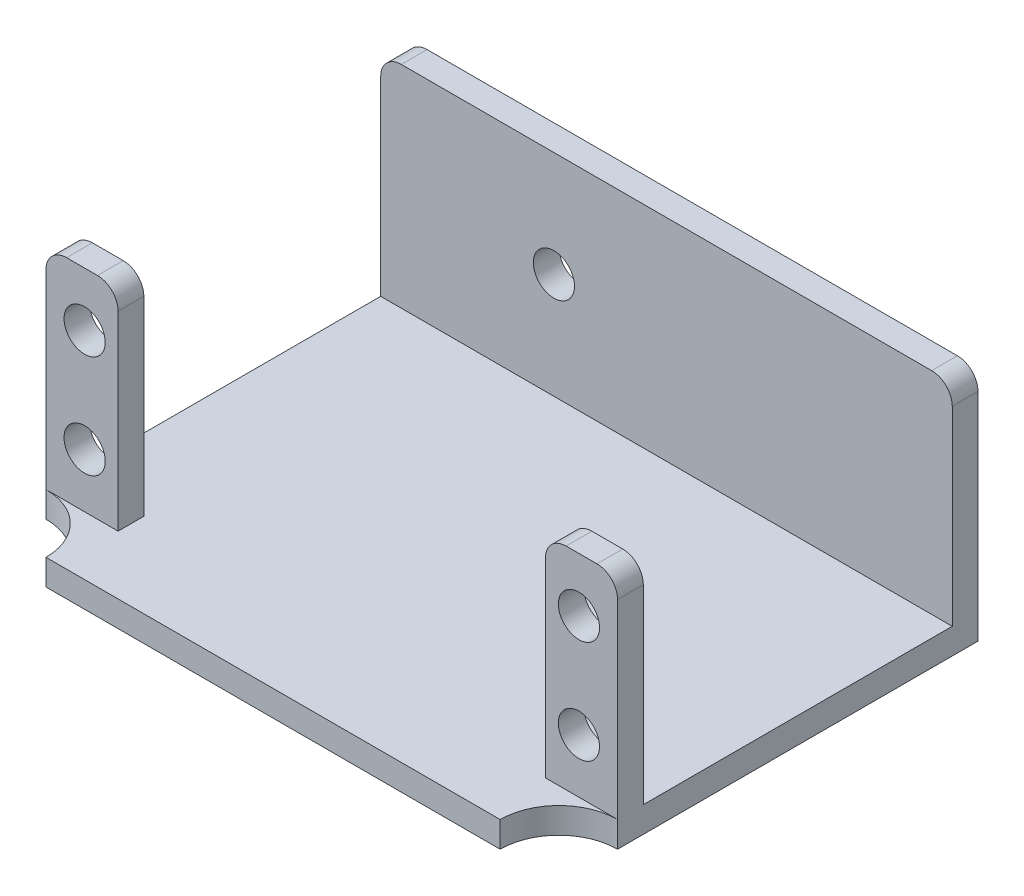
SolidWorks part; units mm, degrees
ref_plane "Front" through (0, 0, 0) normal (0, 0, 1) x (1, 0, 0)
ref_plane "Top" through (0, 0, 0) normal (0, 1, 0) x (1, 0, 0)
ref_plane "Right" through (0, 0, 0) normal (1, 0, 0) x (0, 0, -1)
sketch "Sketch1" plane through (0, 0, 0) normal (0, 1, 0) x (1, 0, 0)
  line L1 (0, 0) -> (55.5, 0)
  line L2 (0, 0) -> (0, 38.2)
  line L3 (0, 38.2) -> (55.5, 38.2)
  line L4 (55.5, 0) -> (55.5, 38.2)
  dimension "D1" = 38.2
  dimension "D2" = 55.5
extrude "bracketBase" add sketch "Sketch1" along normal blind 2.5
ref_plane "referencePlane1" through (0, 0, -8.2) normal (0, 0, 1) x (1, 0, 0)
sketch "Sketch2" plane through (0, 0, -8.2) normal (0, 0, 1) x (1, 0, 0)
  line L0 (27.75, 2.5) -> (27.75, 23) construction
  line L1 (0, 2.5) -> (7, 2.5)
  line L2 (0, 2.5) -> (0, 23)
  line L3 (0, 23) -> (7, 23)
  line L4 (7, 2.5) -> (7, 23)
  line L5 (0, 2.5) -> (55.5, 2.5) construction
  line L6 (55.5, 23) -> (48.5, 23)
  line L7 (48.5, 2.5) -> (48.5, 23)
  line L8 (55.5, 2.5) -> (48.5, 2.5)
  line L9 (55.5, 2.5) -> (55.5, 23)
  dimension "D1" = 20.5
  dimension "D2" = 7
extrude "servoMountingHoleTabs" add sketch "Sketch2" along normal blind 2.5
sketch "Sketch3" plane through (0, 0, -5.7) normal (0, 0, 1) x (1, 0, 0)
  line L0 (0, 12.75) -> (7, 12.75) construction
  line L3 (0, 23) -> (0, 2.5) construction
  line L4 (7, 2.5) -> (7, 23) construction
  line L5 (7, 23) -> (0, 23) construction
  line L6 (27.75, 2.5) -> (27.75, 23) construction
  line L7 (0, 2.5) -> (55.5, 2.5) construction
  circle A0 centre (3.75, 17.75) radius 2
  circle A1 centre (3.75, 7.75) radius 2
  circle A2 centre (51.75, 7.75) radius 2
  circle A3 centre (51.75, 17.75) radius 2
  dimension "D1" = 4
  dimension "D2" = 3.75
  dimension "D3" = 5.25
extrude "servoMountingHoles" cut sketch "Sketch3" against normal blind 2.5
sketch "Sketch4" plane through (0, 0, 0) normal (0, 1, 0) x (1, 0, 0)
  line L0 (55.5, 8.2) -> (55.5, 38.2) construction
  line L1 (0, 38.2) -> (55.5, 38.2)
  line L2 (0, 38.2) -> (0, 40.7)
  line L3 (0, 40.7) -> (55.5, 40.7)
  line L4 (55.5, 38.2) -> (55.5, 40.7)
  dimension "D1" = 2.5
extrude "baseWall" add sketch "Sketch4" along normal up to surface (23 mm away) up to face at (3.5, 23, -6.95)
sketch "Sketch6" plane through (0, 2.5, 0) normal (0, 1, 0) x (1, 0, 0)
  circle A0 centre (0, 0) radius 5.7
  circle A1 centre (55.5, 0) radius 5.7
extrude "baseTrim" cut sketch "Sketch6" against normal blind 2.5
fillet "Fillet1" radius 2 6 edges at (7, 23, -6.95) (48.5, 23, -6.95) (0, 23, -6.95) (55.5, 23, -6.95) (55.5, 23, -39.45) (0, 23, -39.45)
sketch "Sketch7" plane through (0, 0, -40.7) normal (0, 0, -1) x (-1, 0, 0)
  line L0 (0, 21) -> (0, 0) construction
  line L1 (-55.5, 0) -> (0, 0) construction
  circle A0 centre (-16.819, 12.75) radius 2
  dimension "D1" = 4
  dimension "D2" = 16.819
  dimension "D3" = 12.75
extrude "M4mountingHole" cut sketch "Sketch7" against normal blind 10
